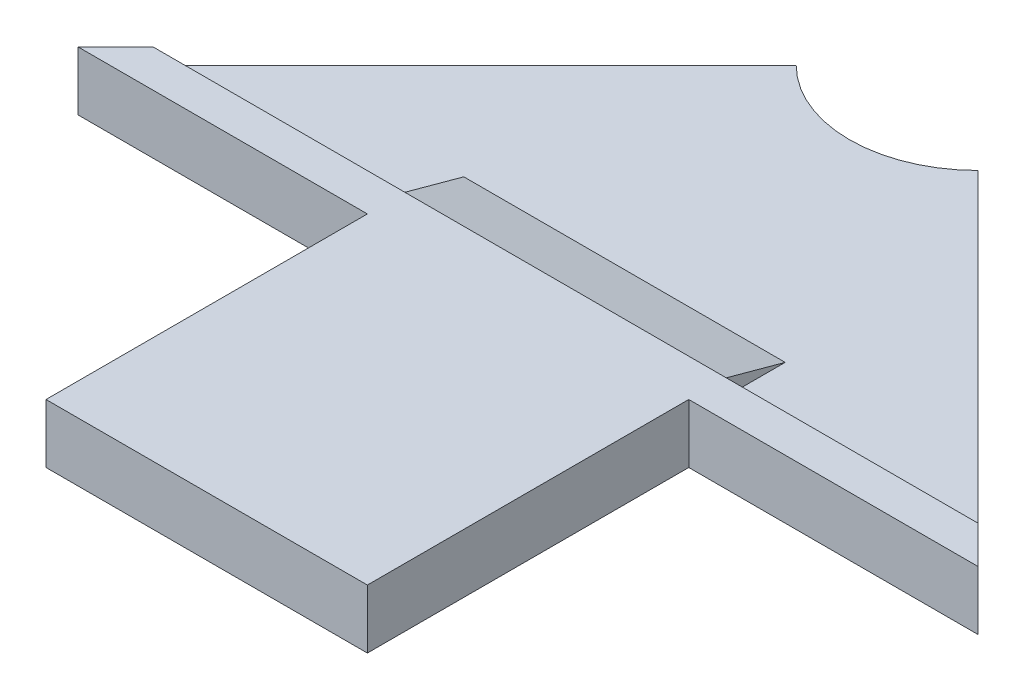
SolidWorks part; units mm, degrees
material "Plain Carbon Steel"
ref_plane "Front Plane" through (0, 0, 0) normal (0, 0, 1) x (1, 0, 0)
ref_plane "Top Plane" through (0, 0, 0) normal (0, 1, 0) x (1, 0, 0)
ref_plane "Right Plane" through (0, 0, 0) normal (1, 0, 0) x (0, 0, -1)
sketch "Sketch1" plane through (0, 0, 0) normal (0, 1, 0) x (1, 0, 0)
  line L0 (-381, -977.9) -> (-381, -838.2)
  line L1 (-381, -838.2) -> (381, -838.2)
  line L2 (-381, -1066.8) -> (381, -1066.8)
  line L3 (-1066.8, -1066.8) -> (-977.9, -977.9)
  line L4 (1066.8, -1066.8) -> (977.9, -977.9)
  line L5 (-381, -1066.8) -> (-381, -1828.8)
  line L6 (381, -838.2) -> (381, -977.9)
  line L7 (-381, -1828.8) -> (381, -1828.8)
  line L8 (-1066.8, -1066.8) -> (-381, -1066.8)
  line L9 (381, -1066.8) -> (1066.8, -1066.8)
  line L10 (381, -977.9) -> (-381, -977.9)
  line L11 (-977.9, -977.9) -> (977.9, -977.9)
  line L12 (-977.9, -977.9) -> (0, 0)
  line L13 (381, -1066.8) -> (381, -1828.8)
  line L14 (0, 0) -> (977.9, -977.9)
  line L15 (0, 0) -> (215.5261, -215.5261)
  line L16 (0, 0) -> (-215.5261, -215.5261)
  arc A1 (-215.5261, -215.5261) -> (215.5261, -215.5261) centre (0, 0) ccw
  point P15 (-381, -908.05)
  point P18 (381, -908.05)
  dimension "D1" = 304.8
extrude "Boss-Extrude1" add sketch "Sketch1" along normal blind 139.7 contours L13 L2 L5 L7 | L11 L3 L8 L2 L9 L4 L10 region at (0, 0, 1022.9942) region at (0, 0, 1447.8)
extrude "Boss-Extrude2" add sketch "Sketch1<10>" along normal blind 101.6 contours L14 L12 L11 L0 L1 L6 | L1 L6 L10 L0 region at (0, 0, 660.8875)
sketch "Sketch1<10>" plane through (0, 0, 0) normal (0, 1, 0) x (1, 0, 0) same geometry as "Sketch1"
ref_plane "Plane2" through (0, 101.6, 0) normal (0, 1, 0) x (1, 0, 0)
sketch "Sketch7" plane through (0, 101.6, 0) normal (0, 1, 0) x (1, 0, 0)
  line L0 (-381, -838.2) -> (381, -838.2)
  line L1 (381, -838.2) -> (381, -977.9)
  line L2 (381, -977.9) -> (-381, -977.9)
  line L3 (-381, -977.9) -> (-381, -838.2)
  line L4 (381, -977.9) -> (0, -977.9)
  line L5 (0, -977.9) -> (0, -838.2)
sketch "Sketch10" plane through (0, 0, 0) normal (1, 0, 0) x (0, 0, -1)
  line L0 (-977.9, 101.6) -> (-977.9, 139.7)
  line L1 (-977.9, 101.6) -> (-838.2, 101.6) construction
  line L2 (-977.9, 139.7) -> (-838.2, 101.6)
  line L3 (-838.2, 101.6) -> (-977.9, 101.6)
extrude "Boss-Extrude4" add sketch "Sketch10" along normal blind 381 and the other way blind 381
